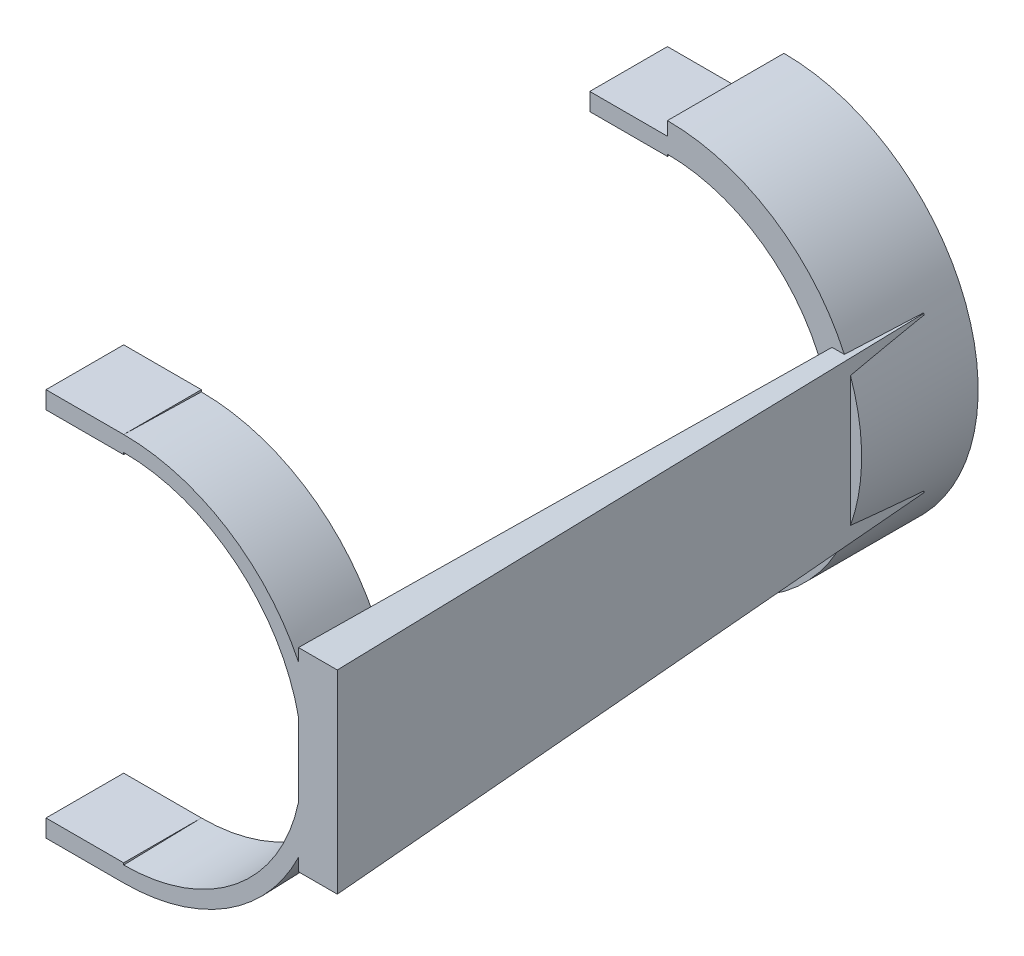
SolidWorks part; units mm, degrees
ref_plane "Front" through (0, 0, 0) normal (0, 0, 1) x (1, 0, 0)
ref_plane "Top" through (0, 0, 0) normal (0, 1, 0) x (1, 0, 0)
ref_plane "Right" through (0, 0, 0) normal (1, 0, 0) x (0, 0, -1)
sketch "草图1" plane through (0, 0, 0) normal (1, 0, 0) x (0, 0, -1)
  line L0 (0, 46) -> (0, 75.0518) construction
  line L1 (0, 0) -> (-171.072, 0) construction
  line L2 (0, 50) -> (0, 46)
  line L3 (160, 42) -> (160, 46)
  line L4 (0, 0) -> (160, 0)
  line L5 (0, 50) -> (160, 46)
  line L6 (0, 46) -> (160, 42)
  point P7 (0, 46)
  point P8 (160, 42)
  dimension "D1" = 50
  dimension "D2" = 160
  dimension "D3" = 46
  dimension "D4" = 46
  dimension "D5" = 42
revolve "旋转1" add sketch "草图1" angle 180 about L4 region at (0, 46, -80)
sketch "草图2" plane through (0, 0, 0) normal (1, 0, 0) x (0, 0, -1)
  line L0 (0, 50) -> (0, -50) construction
  line L1 (160, 46) -> (160, -46) construction
  line L3 (20, 60.115) -> (140, 60.115)
  line L4 (20, 60.115) -> (20, -64.3514)
  line L5 (20, -64.3514) -> (140, -64.3514)
  line L6 (140, 60.115) -> (140, -64.3514)
  dimension "D1" = 20
  dimension "D2" = 20
extrude "切除-拉伸1" cut sketch "草图2" along normal through all
sketch "草图3" plane through (0, 0, 0) normal (0, 0, 1) x (1, 0, 0)
  line L0 (0, 0) -> (53.4175, 0) construction
  line L2 (55, 25) -> (45, 25)
  line L3 (55, 25) -> (55, -25)
  line L4 (55, -25) -> (45, -25)
  line L5 (45, 25) -> (45, -25)
  dimension "D1" = 50
  dimension "D2" = 25
  dimension "D3" = 10
  dimension "D4" = 55
sketch "草图4" plane through (0, 0, -160) normal (0, 0, -1) x (-1, 0, 0)
  line L0 (0, 0) -> (-66.5571, 0) construction
  line L2 (-46, 20) -> (-42, 20)
  line L3 (-46, 20) -> (-46, -20)
  line L4 (-46, -20) -> (-42, -20)
  line L5 (-42, 20) -> (-42, -20)
  dimension "D1" = 46
  dimension "D2" = 4
  dimension "D3" = 40
  dimension "D4" = 20
loft "放样1" add profiles "草图3", "草图4" connector at (55, 25, 0) connector at (46, 20, -160)
sketch "草图6" plane through (0, 0, 0) normal (-1, 0, 0) x (0, 0, 1)
  line L0 (-20, -45.5) -> (-20, -49.5) construction
  line L1 (-20, 45.5) -> (0, 45.5)
  line L2 (-20, 45.5) -> (-20, 50)
  line L3 (-20, 50) -> (0, 50)
  line L4 (0, 45.5) -> (0, 50)
  line L5 (0, -50) -> (-20, -50)
  line L6 (0, -50) -> (0, -45.5)
  line L7 (0, -45.5) -> (-20, -45.5)
  line L8 (-20, -50) -> (-20, -45.5)
  line L9 (0, -46) -> (-20, -45.5) construction
  line L11 (-140, -46.5) -> (-160, -46.5)
  line L12 (-140, -46.5) -> (-140, -42)
  line L13 (-140, -42) -> (-160, -42)
  line L14 (-160, -46.5) -> (-160, -42)
  line L15 (-140, 46.5) -> (-160, 46.5)
  line L16 (-140, 46.5) -> (-140, 42)
  line L17 (-140, 42) -> (-160, 42)
  line L18 (-160, 46.5) -> (-160, 42)
extrude "凸台-拉伸1" add sketch "草图6" along normal blind 20
sketch "草图8" plane through (0, 0, -140) normal (0, 0, 1) x (1, 0, 0)
  line L0 (0, 46) -> (0, 50)
  line L1 (0, -46) -> (0, -50)
  arc A0 (0, -46) -> (0, 46) centre (0, 0) ccw
  arc A1 (0, -50) -> (0, 50) centre (0, 0) ccw
extrude "凸台-拉伸3" add sketch "草图8" against normal blind 30
